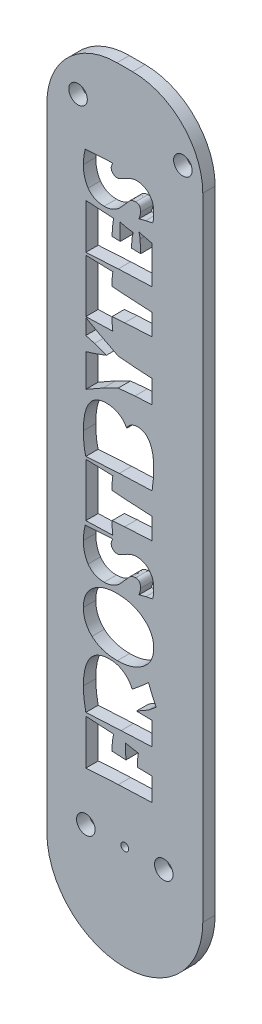
SolidWorks part; units mm, degrees
material "Pine"
ref_plane "Front" through (0, 0, 0) normal (0, 0, 1) x (1, 0, 0)
ref_plane "Top" through (0, 0, 0) normal (0, 1, 0) x (1, 0, 0)
ref_plane "Right" through (0, 0, 0) normal (1, 0, 0) x (0, 0, -1)
sketch "Sketch2" plane through (0, 0, 0) normal (0, 0, 1) x (1, 0, 0)
  line L1 (-20, -100) -> (20, -100)
  line L2 (-20, -100) -> (-20, 100)
  line L3 (-20, 100) -> (20, 100)
  line L4 (20, -100) -> (20, 100)
  line L5 (-20, -100) -> (20, 100) construction
  line L6 (-20, 100) -> (20, -100) construction
  point P1 (0, 0)
  dimension "D1" = 200
  dimension "D2" = 40
extrude "Boss-Extrude1" add sketch "Sketch2" along normal blind 3.175
sketch "Sketch3" plane through (0, 0, 0) normal (0, 0, -1) x (-1, 0, 0)
  line L0 (20, -100) -> (-20, -100) construction
  line L1 (1.325, -88.5019) -> (-1.325, -88.5019)
  arc A0 (-1.325, -88.5019) -> (1.325, -88.5019) centre (0, -90) ccw
  dimension "D1" = 4
  dimension "D2" = 10
  dimension "D3" = 2.65
fillet "Fillet1" radius 20 2 edges at (20, -100, 1.5875) (-20, -100, 1.5875)
fillet "Fillet2" radius 18 2 edges at (20, 100, 1.5875) (-20, 100, 1.5875)
sketch "Sketch7" plane through (0, 0, 3.175) normal (0, 0, 1) x (1, 0, 0)
  line L0 (-30.4029, 88) -> (30.4029, 88) construction
  line L1 (-12, 88) -> (14.8973, 85.6468) construction
  circle A0 centre (-12, 88) radius 2.38
  circle A3 centre (14.8973, 85.6468) radius 2.38
  point P4 (0, 88)
  dimension "D2" = 4.76
  dimension "D3" = 12
  dimension "D7" = 4.76
  dimension "D5" = 5
  dimension "D6" = 27
extrude "Cut-Extrude5" cut sketch "Sketch7" against normal through all
sketch "Sketch8" plane through (0, 0, 3.175) normal (0, 0, 1) x (1, 0, 0)
  line L0 (0, -90) -> (0, -49.3452) construction
  line L1 (-10, -73.25) -> (0, -73.25) construction
  line L2 (0, -73.25) -> (10, -73.25) construction
  circle A12 centre (0, -73.25) radius 1
  circle A13 centre (10, -73.25) radius 2.38
  circle A14 centre (-10, -73.25) radius 2.38
  dimension "D2" = 4.76
  dimension "D14" = 2
  dimension "D3" = 4.76
  dimension "D4" = 10
  dimension "D5" = 10
extrude "Cut-Extrude6" cut sketch "Sketch8" against normal through all
sketch "Sketch9" plane through (0, 0, 3.175) normal (0, 0, 1) x (1, 0, 0)
  line L0 (0, -100) -> (0, 100) construction
  line L1 (2, 100) -> (-2, 100) construction
  line L2 (7, -75) -> (7, 75) construction
  line L3 (7, 0) -> (0, 0) construction
  text T0 "   FROSTBYTES" font "Showcard Gothic" height 17
  dimension "D2" = 90
  dimension "D1" = 150
  dimension "D3" = 7
extrude "Cut-Extrude8" cut sketch "Sketch9" against normal blind 10 body kept at (-20, 82, 0)
